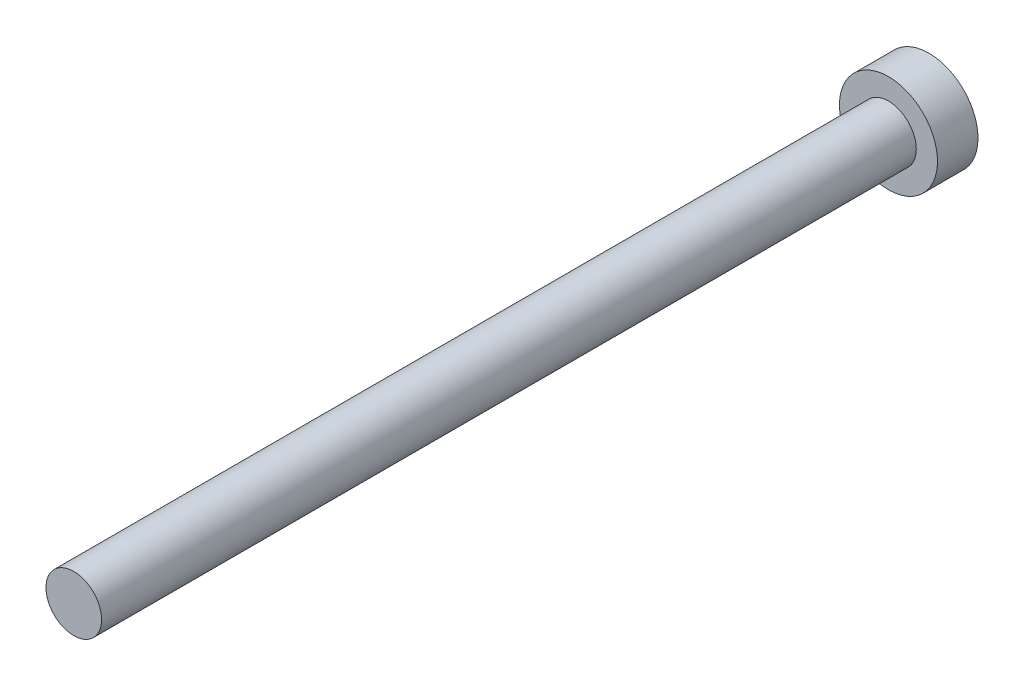
SolidWorks part; units mm, degrees
ref_plane "Front Plane" through (0, 0, 0) normal (0, 0, 1) x (1, 0, 0)
ref_plane "Top Plane" through (0, 0, 0) normal (0, 1, 0) x (1, 0, 0)
ref_plane "Right Plane" through (0, 0, 0) normal (1, 0, 0) x (0, 0, -1)
sketch "Sketch1" plane through (0, 0, 0) normal (0, 0, 1) x (1, 0, 0)
  circle A0 centre (0, 0) radius 1.5
  dimension "D1" = 3
extrude "Boss-Extrude1" add sketch "Sketch1" along normal blind 42
sketch "Sketch2" plane through (0, 0, 0) normal (0, 0, -1) x (-1, 0, 0)
  circle A0 centre (0, 0) radius 2.75
  dimension "D1" = 5.5
extrude "Boss-Extrude2" add sketch "Sketch2" against normal blind 2.2
scale "Escala1" scale about origin uniform scaling yes scale factor 1.5
scale "Escala2" scale about origin uniform scaling yes scale factor 1.5
sketch "Croquis1" plane through (0, 0, 94.5) normal (0, 0, 1) x (1, 0, 0)
  circle A2 centre (0, 0) radius 3.375 construction
  circle A3 centre (0, 0) radius 3.375 construction
  circle A4 centre (0, 0) radius 3.4
  dimension "D1" = 6.8
extrude "Saliente-Extruir1" add sketch "Croquis1" along normal blind 10 and the other way up to next
sketch "Croquis2" plane through (0, 0, 0) normal (0, 0, -1) x (-1, 0, 0)
  circle A0 centre (0, 0) radius 5.99
  dimension "D1" = 11.98
extrude "Cortar-Extruir1" cut sketch "Croquis2" against normal through all both and the other way through all flip side to cut
